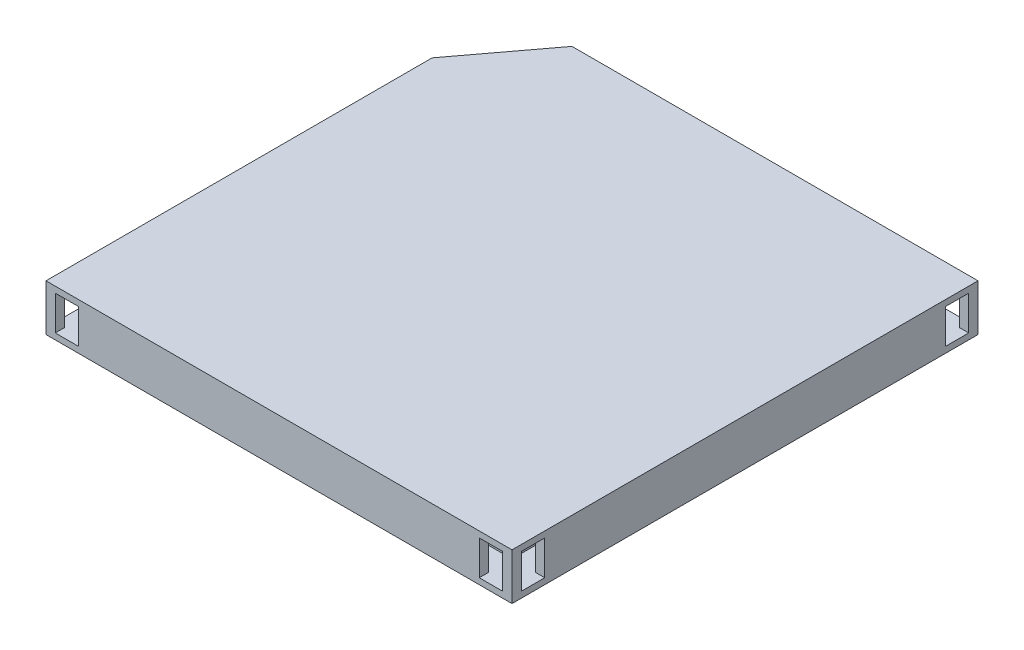
SolidWorks part; units mm, degrees
ref_plane "Front Plane" through (0, 0, 0) normal (0, 0, 1) x (1, 0, 0)
ref_plane "Top Plane" through (0, 0, 0) normal (0, 1, 0) x (1, 0, 0)
ref_plane "Right Plane" through (0, 0, 0) normal (1, 0, 0) x (0, 0, -1)
sketch "Sketch1" plane through (0, 0, 0) normal (0, 0, 1) x (1, 0, 0)
  line L1 (-50, -5) -> (50, -5)
  line L2 (-50, -5) -> (-50, 5)
  line L3 (-50, 5) -> (50, 5)
  line L4 (50, -5) -> (50, 5)
  line L5 (-50, -5) -> (50, 5) construction
  line L6 (-50, 5) -> (50, -5) construction
  line L7 (0, 26.9701) -> (0, -31.5295) construction
  line L8 (-55.533, 0) -> (70.4908, 0) construction
  point P1 (0, 0)
  point P10 (50, 0)
  point P11 (0, 5)
  dimension "D1" = 100
  dimension "D2" = 10
extrude "Boss-Extrude1" add sketch "Sketch1" along normal mid plane 100
sketch "Sketch2" plane through (0, 0, 50) normal (0, 0, 1) x (1, 0, 0)
  line L1 (42.9788, -3.6997) -> (48.0105, -3.6997)
  line L2 (42.9788, -3.6997) -> (42.9788, 3.6997)
  line L3 (42.9788, 3.6997) -> (48.0105, 3.6997)
  line L4 (48.0105, -3.6997) -> (48.0105, 3.6997)
  line L5 (42.9788, -3.6997) -> (48.0105, 3.6997) construction
  line L6 (42.9788, 3.6997) -> (48.0105, -3.6997) construction
  point P0 (45.4947, 0)
extrude "Cut-Extrude1" cut sketch "Sketch2" against normal through all
ref_axis "Axis1" through (-50, 5, -50) along (0.7071, 0, 0.7071)
ref_plane "Plane1" through (0, 0, 0) normal (-0.7071, 0, 0.7071) x (0.7071, 0, 0.7071)
ref_axis "Axis2" through (50, 5, -50) along (-0.7071, 0, 0.7071)
ref_plane "Plane2" through (0, 0, 0) normal (-0.7071, 0, -0.7071) x (-0.7071, 0, 0.7071)
mirror "Mirror1" about plane through (0, 0, 0) normal (-0.7071, 0, 0.7071) of "Cut-Extrude1"
mirror "Mirror2" about plane through (0, 0, 0) normal (-0.7071, 0, -0.7071) of "Mirror1"
sketch "Sketch3" plane through (0, 5, 0) normal (0, 1, 0) x (1, 0, 0)
  line L0 (-53.9443, 27.6064) -> (-24.6965, 66.5537)
extrude "Cut-Extrude2" cut sketch "Sketch3" against normal through all
